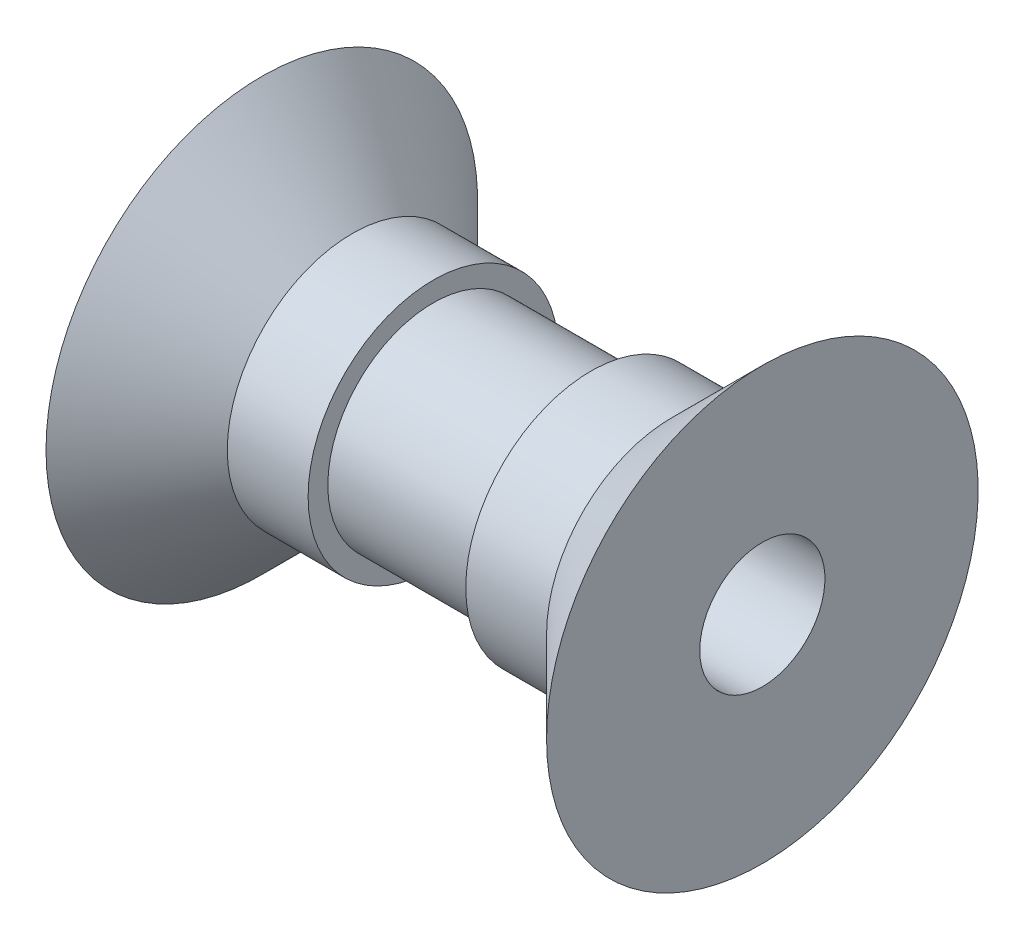
SolidWorks part; units mm, degrees
ref_plane "Front Plane" through (0, 0, 0) normal (0, 0, 1) x (1, 0, 0)
ref_plane "Top Plane" through (0, 0, 0) normal (0, 1, 0) x (1, 0, 0)
ref_plane "Right Plane" through (0, 0, 0) normal (1, 0, 0) x (0, 0, -1)
sketch "Sketch1" plane through (0, 0, 0) normal (0, 0, 1) x (1, 0, 0)
  line L0 (-93.9518, 0) -> (103.338, 0) construction
  line L1 (-6.35, 0) -> (-6.35, 5.475)
  line L2 (-6.35, 5.475) -> (-4.05, 3.175)
  line L3 (-4.05, 3.175) -> (-2, 3.175)
  line L4 (-2, 3.175) -> (-2, 2.675)
  line L5 (-2, 2.675) -> (2, 2.675)
  line L6 (0, -10.0179) -> (0, 20.3066) construction
  line L7 (93.9518, 0) -> (-103.338, 0) construction
  line L8 (2, 3.175) -> (2, 2.675)
  line L9 (4.05, 3.175) -> (2, 3.175)
  line L10 (6.35, 5.475) -> (4.05, 3.175)
  line L11 (6.35, 0) -> (6.35, 5.475)
  line L12 (-6.35, 0) -> (6.35, 0)
  point P14 (0, 2.675)
  dimension "D1" = 6.35
  dimension "D2" = 4
  dimension "D3" = 8.1
  dimension "D4" = 0.5
  dimension "D5" = 135
  dimension "D6" = 3.175
revolve "Revolve1" add sketch "Sketch1" angle 360 about L0
sketch "Sketch2" plane through (-6.35, 0, 0) normal (-1, 0, 0) x (0, 0, 1)
  circle A0 centre (0, 0) radius 1.5875
  dimension "D1" = 3.175
extrude "Cut-Extrude1" cut sketch "Sketch2" against normal through all
sketch "Sketch3" plane through (6.35, 0, 0) normal (1, 0, 0) x (0, 0, -1)
  circle A0 centre (0, 0) radius 17.4353
extrude "Cut-Extrude2" [suppressed] cut sketch "Sketch3" against normal up to vertex up to point (0, 0, 0)
sketch "Sketch4" [suppressed] plane through (0, 0, 0) normal (1, 0, 0) x (0, 0, -1)
  line L0 (0, 3.9269) -> (0, -4.4745) construction
  line L1 (-4.3015, 0) -> (4.5177, 0) construction
